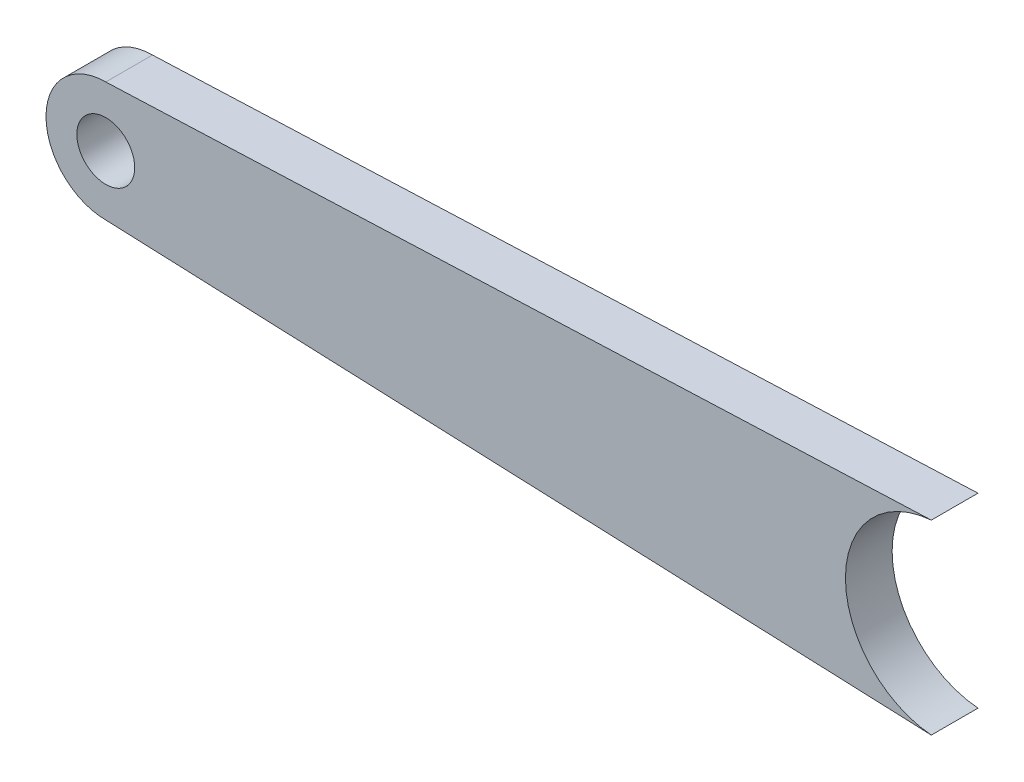
SolidWorks part; units mm, degrees
ref_plane "Front Plane" through (0, 0, 0) normal (0, 0, 1) x (1, 0, 0)
ref_plane "Top Plane" through (0, 0, 0) normal (0, 1, 0) x (1, 0, 0)
ref_plane "Right Plane" through (0, 0, 0) normal (1, 0, 0) x (0, 0, -1)
sketch "Sketch1" plane through (0, 0, 0) normal (0, 0, 1) x (1, 0, 0)
  circle A0 centre (0, 0) radius 3.937
  circle A1 centre (0, 0) radius 8.128
  dimension "D1" = 7.874
  dimension "D2" = 16.256
extrude "Boss-Extrude1" add sketch "Sketch1" along normal blind 6.35
sketch "Sketch2" plane through (0, 0, 6.35) normal (0, 0, 1) x (1, 0, 0)
  line L0 (0, 8.128) -> (113.284, 12.7)
  line L1 (0, -8.128) -> (113.284, -12.7)
  circle A0 centre (113.284, 0) radius 12.7
  circle A1 centre (0, 0) radius 8.128 construction
  arc A2 (113.284, 12.7) -> (113.284, -12.7) centre (113.284, 0) ccw
  arc A3 (0, 8.128) -> (0, -8.128) centre (0, 0) cw
  circle M1 centre (0, 0) radius 8.128
  dimension "D1" = 25.4
  dimension "D2" = 113.284
extrude "Boss-Extrude2" add sketch "Sketch2" against normal blind 6.35 contours A0 L0 L1 M1 region at (57.798, 0, 6.35)
